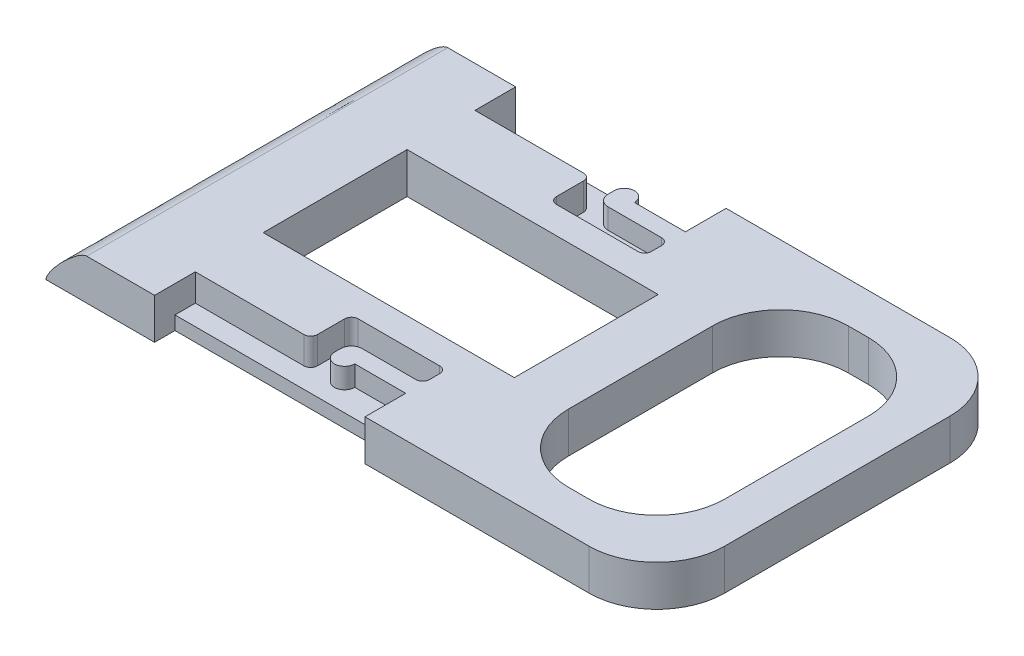
SolidWorks part; units mm, degrees
ref_plane "Front Plane" through (0, 0, 0) normal (0, 0, 1) x (1, 0, 0)
ref_plane "Top Plane" through (0, 0, 0) normal (0, 1, 0) x (1, 0, 0)
ref_plane "Right Plane" through (0, 0, 0) normal (1, 0, 0) x (0, 0, -1)
sketch "Sketch1" plane through (0, 0, 0) normal (0, 1, 0) x (1, 0, 0)
  line L1 (0, 0) -> (45, 0)
  line L2 (0, 0) -> (0, 26.6)
  line L3 (0, 26.6) -> (45, 26.6)
  line L4 (45, 0) -> (45, 26.6)
  dimension "D1" = 45
  dimension "D2" = 26.6
extrude "Boss-Extrude1" add sketch "Sketch1" along normal blind 3
sketch "Sketch3" plane through (0, 3, 0) normal (0, 1, 0) x (1, 0, 0)
  line L0 (45, 26.6) -> (0, 26.6) construction
  line L1 (8, 26.6) -> (23.5, 26.6)
  line L2 (8, 26.6) -> (8, 23.6)
  line L3 (8, 23.6) -> (23.5, 23.6)
  line L4 (23.5, 26.6) -> (23.5, 23.6)
  line L5 (0, 0) -> (45, 0) construction
  line L6 (8, 0) -> (23.5, 0)
  line L7 (8, 0) -> (8, 3)
  line L8 (8, 3) -> (23.5, 3)
  line L9 (23.5, 0) -> (23.5, 3)
  line L10 (0, 26.6) -> (0, 0) construction
  dimension "D1" = 8
  dimension "D2" = 3
  dimension "D3" = 23.5
extrude "Cut-Extrude1" cut sketch "Sketch3" against normal offset from surface (2 mm away) 1 up to face at (22.5, 0, -13.3)
sketch "Sketch4" plane through (0, 1, 0) normal (0, 1, 0) x (1, 0, 0)
  line L0 (23.5, 0) -> (23.5, 3) construction
  line L1 (8, 0) -> (23.5, 0)
  line L2 (8, 0) -> (8, 1.5)
  line L3 (8, 1.5) -> (23.5, 1.5)
  line L4 (23.5, 0) -> (23.5, 1.5)
  line L5 (23.5, 23.6) -> (23.5, 26.6) construction
  line L6 (8, 26.6) -> (23.5, 26.6)
  line L7 (8, 26.6) -> (8, 25.1)
  line L8 (8, 25.1) -> (23.5, 25.1)
  line L9 (23.5, 26.6) -> (23.5, 25.1)
  dimension "D1" = 1.5
extrude "Cut-Extrude2" cut sketch "Sketch4" against normal through all
fillet "Fillet1" radius 3 1 edges at (0, 3, -13.3) conic radius 10
sketch "Sketch5" plane through (0, 3, 0) normal (0, 1, 0) x (1, 0, 0)
  line L1 (23.5, 3) -> (8, 3) construction
  line L2 (8, 23.6) -> (23.5, 23.6) construction
  line L3 (23.5, 0) -> (23.5, 3) construction
  circle A1 centre (19, 3) radius 0.75
  circle A2 centre (19, 23.6) radius 0.75
  point P11 (0, 0)
  dimension "D1" = 1.5
  dimension "D2" = 4.5
extrude "Boss-Extrude2" add sketch "Sketch5" against normal up to next
sketch "Sketch6" plane through (0, 3, 0) normal (0, 1, 0) x (1, 0, 0)
  line L0 (8, 26.6) -> (8, 23.6) construction
  line L1 (26.5, 18.6) -> (8, 18.6)
  line L2 (26.5, 18.6) -> (26.5, 8)
  line L3 (26.5, 8) -> (8, 8)
  line L4 (8, 18.6) -> (8, 8)
  line L5 (23.5, 23.6) -> (23.5, 26.6) construction
  line L6 (8, 23.6) -> (18.25, 23.6) construction
  line L7 (18.25, 3) -> (8, 3) construction
  dimension "D1" = 3
  dimension "D2" = 5
  dimension "D3" = 5
extrude "Cut-Extrude3" cut sketch "Sketch6" against normal through all
sketch "Sketch7" plane through (0, 3, 0) normal (0, 1, 0) x (1, 0, 0)
  line L0 (26.5, 13.3) -> (8, 13.3) construction
  line L1 (26.5, 8) -> (26.5, 18.6) construction
  line L2 (8, 18.6) -> (8, 8) construction
  line L3 (18.25, 3) -> (16.5, 3)
  line L4 (18.25, 3) -> (8, 3) construction
  line L5 (16.5, 3) -> (16.5, 6)
  line L6 (16.5, 6) -> (23.5, 6)
  line L7 (23.5, 6) -> (23.5, 4.25)
  line L8 (23.5, 4.25) -> (18.25, 4.25)
  line L9 (18.25, 4.25) -> (18.25, 3)
  line L10 (23.5, 1.5) -> (23.5, 3) construction
  line L11 (23.5, 3) -> (19.75, 3) construction
  line L12 (18.25, 22.35) -> (18.25, 23.6)
  line L13 (23.5, 22.35) -> (18.25, 22.35)
  line L14 (23.5, 20.6) -> (23.5, 22.35)
  line L15 (16.5, 20.6) -> (23.5, 20.6)
  line L16 (16.5, 23.6) -> (16.5, 20.6)
  line L17 (18.25, 23.6) -> (16.5, 23.6)
  dimension "D1" = 1.25
  dimension "D2" = 7
extrude "Cut-Extrude4" cut sketch "Sketch7" against normal up to surface (2 mm away) up to face at (16.8333, 1, -2.375)
sketch "Sketch8" plane through (0, 0, -3) normal (0, 0, 1) x (1, 0, 0)
  line L0 (18.25, 3) -> (18.25, 1) construction
  line L1 (23.5, 1) -> (18.25, 1)
  line L2 (23.5, 1) -> (23.5, 1.5)
  line L3 (23.5, 1.5) -> (18.25, 1.5)
  line L4 (18.25, 1) -> (18.25, 1.5)
  dimension "D1" = 0.5
extrude "Cut-Extrude5" cut sketch "Sketch8" against normal up to next and the other way up to next
sketch "Sketch9" plane through (0, 0, -23.6) normal (0, 0, -1) x (-1, 0, 0)
  line L0 (-18.25, 1) -> (-18.25, 3) construction
  line L1 (-23.5, 1) -> (-18.25, 1)
  line L2 (-23.5, 1) -> (-23.5, 1.5)
  line L3 (-23.5, 1.5) -> (-18.25, 1.5)
  line L4 (-18.25, 1) -> (-18.25, 1.5)
  line L5 (-23.5, 1.5) -> (-19.75, 1.5) construction
extrude "Cut-Extrude6" cut sketch "Sketch9" against normal up to next and the other way up to next
fillet "Fillet2" radius 0.8 2 edges at (18.25, 2.25, -4.25) (18.25, 2.25, -22.35)
fillet "Fillet3" radius 5 2 edges at (45, 1.5, 0) (45, 1.5, -26.6)
sketch "Sketch10" plane through (0, 3, 0) normal (0, 1, 0) x (1, 0, 0)
  line L0 (26.5, 8) -> (26.5, 18.6) construction
  line L1 (42, 23.6) -> (30.5, 23.6)
  line L2 (42, 23.6) -> (42, 3)
  line L3 (42, 3) -> (30.5, 3)
  line L4 (30.5, 23.6) -> (30.5, 3)
  line L5 (45, 5) -> (45, 21.6) construction
  line L6 (23.5, 0) -> (40, 0) construction
  line L7 (40, 26.6) -> (23.5, 26.6) construction
  dimension "D1" = 4
  dimension "D2" = 3
  dimension "D3" = 3
  dimension "D4" = 3
extrude "Cut-Extrude7" cut sketch "Sketch10" against normal through all
fillet "Fillet4" radius 5 4 edges at (42, 1.5, -3) (42, 1.5, -23.6) (30.5, 1.5, -23.6) (30.5, 1.5, -3)
fillet "Fillet5" radius 0.5 8 edges at (16.5, 2, -3) (16.5, 2, -23.6) (16.5, 2, -20.6) (23.5, 2, -20.6) (23.5, 2, -6) (16.5, 2, -6) (23.5, 2.25, -22.35) (23.5, 2.25, -4.25)
